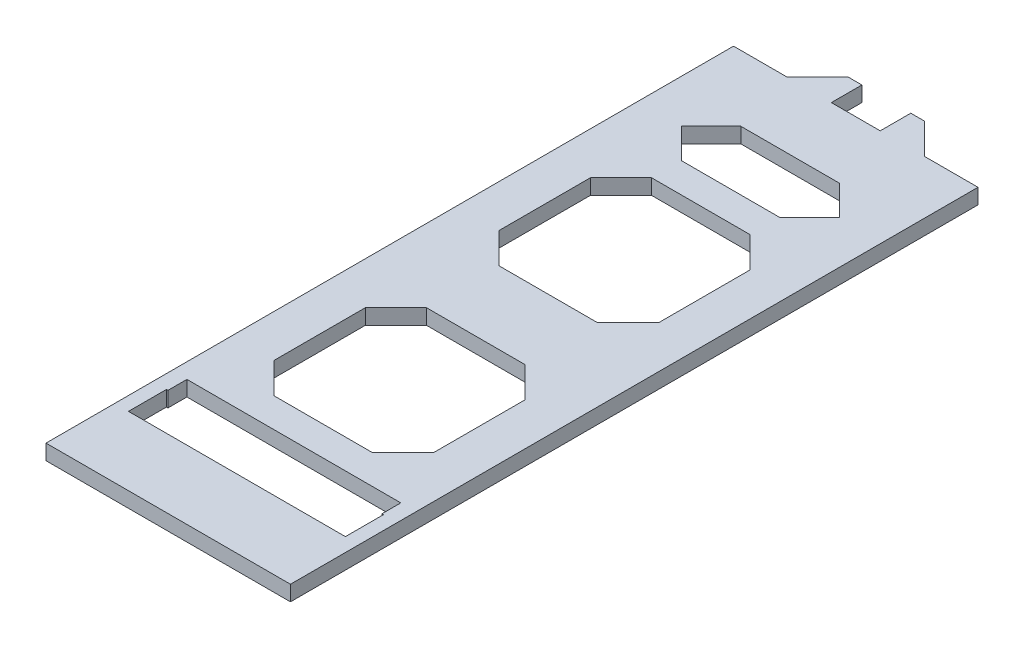
SolidWorks part; units mm, degrees
ref_plane "Front Plane" through (0, 0, 0) normal (0, 0, 1) x (1, 0, 0)
ref_plane "Top Plane" through (0, 0, 0) normal (0, 1, 0) x (1, 0, 0)
ref_plane "Right Plane" through (0, 0, 0) normal (1, 0, 0) x (0, 0, -1)
sketch "Sketch1" plane through (0, 0, 0) normal (0, 1, 0) x (1, 0, 0)
  line L0 (-8, 112.5) -> (8, 112.5)
  line L1 (-40, 112.5) -> (-12.5, 112.5)
  line L2 (-40, 112.5) -> (-40, -112.5)
  line L3 (-40, -112.5) -> (40, -112.5)
  line L4 (40, 112.5) -> (40, -112.5)
  line L5 (-12.5, 122.5) -> (-8, 122.5)
  line L6 (-12.5, 122.5) -> (-12.5, 112.5)
  line L8 (-35, -71.3868) -> (35, -71.3868)
  line L9 (-35, -71.3868) -> (-35, -77.5967)
  line L11 (35, -71.3868) -> (35, -77.5967)
  line L12 (12.5, 122.5) -> (12.5, 112.5)
  line L13 (-12.5, 122.5) -> (-8, 118.9) construction
  line L14 (-35.5, -90.0166) -> (35.5, -90.0166)
  line L15 (-35.5, -90.0166) -> (-35.5, -77.5967)
  line L16 (-35.5, -77.5967) -> (-35, -77.5967)
  line L17 (35.5, -90.0166) -> (35.5, -77.5967)
  line L18 (-8, 112.5) -> (8, 112.5)
  line L19 (-8, 112.5) -> (-8, 122.5)
  line L21 (8, 122.5) -> (8, 112.5)
  line L22 (35, -77.5967) -> (35.5, -77.5967)
  line L23 (8, 122.5) -> (12.5, 122.5)
  line L24 (12.5, 112.5) -> (40, 112.5)
  line L25 (8, 118.9) -> (12.5, 122.5) construction
  point P0 (0, 0)
  point P8 (0, -77.5967)
  point P9 (0, 112.5)
  point P13 (0, -83.8066)
  point P24 (0, 112.5)
  point P25 (0, 112.5)
  dimension "D1" = 70
  dimension "D2" = 80
  dimension "225" = 225
  dimension "D3" = 71
extrude "Boss-Extrude1" add sketch "Sketch1" along normal blind 5 contours L24 L12 L23 L21 L0 L19 L5 L6 L1 L2 L3 L4 L11 L22 L17 L14 L15 L16 L9 L8 region at (0, 0, -6.9668)
chamfer "Chamfer1" distance 10 angle 45 2 edges at (-12.5, 2.5, -112.5) (12.5, 2.5, -112.5)
sketch "Sketch2" plane through (0, 5, 0) normal (0, 1, 0) x (1, 0, 0)
  line L0 (-26.1201, 11.8726) -> (-26.1201, 61.7828)
  line L1 (-26.1201, -61.7828) -> (26.1201, -61.7828)
  line L2 (-26.1201, -61.7828) -> (-26.1201, -11.8726)
  line L3 (-26.1201, 61.7828) -> (26.1201, 61.7828)
  line L4 (26.1201, -61.7828) -> (26.1201, -11.8726)
  line L5 (-26.1201, -61.7828) -> (-5.0194, -11.8726) construction
  line L6 (-26.1201, 61.7828) -> (0, 0) construction
  line L7 (-26.1201, 90.9853) -> (26.1201, 90.9853)
  line L8 (-26.1201, 90.9853) -> (-26.1201, 71.517)
  line L9 (-26.1201, 71.517) -> (26.1201, 71.517)
  line L10 (26.1201, 90.9853) -> (26.1201, 71.517)
  line L11 (-26.1201, 90.9853) -> (26.1201, 71.517) construction
  line L12 (-26.1201, 71.517) -> (26.1201, 90.9853) construction
  line L13 (-26.1201, 11.8726) -> (26.1201, 11.8726)
  line L15 (-26.1201, -11.8726) -> (26.1201, -11.8726)
  line L17 (-26.1201, 11.8726) -> (0, 0) construction
  line L18 (0, 0) -> (26.1201, 11.8726) construction
  line L19 (0, 0) -> (26.1201, 61.7828) construction
  line L20 (5.0194, -11.8726) -> (26.1201, -61.7828) construction
  line L21 (26.1201, 11.8726) -> (26.1201, 61.7828)
  point P0 (0, 0)
  point P5 (0, 81.2511)
  point P11 (0, 0)
extrude "Cut-Extrude1" cut sketch "Sketch2" against normal blind 5
chamfer "Chamfer2" distance 10 angle 45 12 edges at (-26.1201, 2.5, -71.517) (26.1201, 2.5, -71.517) (-26.1201, 2.5, 61.7828) (26.1201, 2.5, 11.8726) (26.1201, 2.5, 61.7828) (-26.1201, 2.5, 11.8726) (-26.1201, 2.5, -90.9853) (-26.1201, 2.5, -61.7828) (26.1201, 2.5, -61.7828) (26.1201, 2.5, -90.9853) (26.1201, 2.5, -11.8726) (-26.1201, 2.5, -11.8726)
